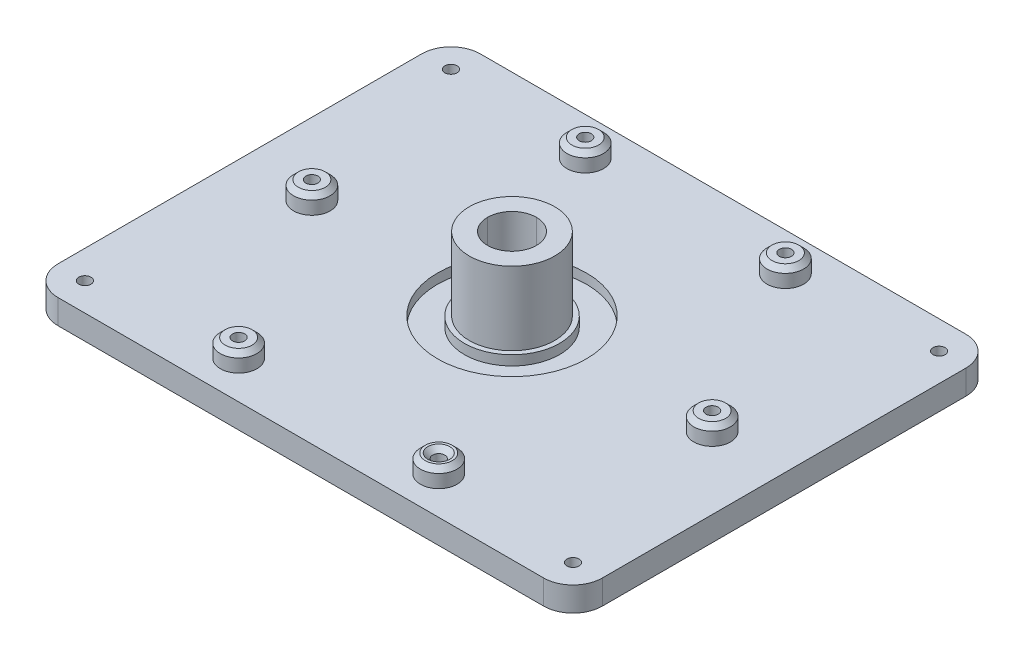
SolidWorks part; units mm, degrees
ref_plane "Front Plane" through (0, 0, 0) normal (0, 0, 1) x (1, 0, 0)
ref_plane "Top Plane" through (0, 0, 0) normal (0, 1, 0) x (1, 0, 0)
ref_plane "Right Plane" through (0, 0, 0) normal (1, 0, 0) x (0, 0, -1)
sketch "Sketch1" plane through (0, 0, 0) normal (0, 1, 0) x (1, 0, 0)
  line L1 (-100, 75) -> (100, 75) construction
  line L2 (-100, 75) -> (-100, -75) construction
  line L3 (-100, -75) -> (100, -75) construction
  line L4 (100, 75) -> (100, -75) construction
  line L5 (-100, 75) -> (100, -75) construction
  line L6 (-100, -75) -> (100, 75) construction
  line L7 (-99.5, 86.5) -> (99.5, 86.5)
  line L8 (-111.5, 74.5) -> (-111.5, -74.5)
  line L9 (-99.5, -86.5) -> (99.5, -86.5)
  line L10 (111.5, 74.5) -> (111.5, -74.5)
  line L11 (-111.5, 86.5) -> (111.5, -86.5) construction
  line L12 (-111.5, -86.5) -> (111.5, 86.5) construction
  circle A0 centre (100, 75) radius 2.5
  circle A1 centre (100, -75) radius 2.5
  circle A2 centre (-100, -75) radius 2.5
  circle A3 centre (-100, 75) radius 2.5
  arc A4 (99.5, -86.5) -> (111.5, -74.5) centre (99.5, -74.5) ccw
  arc A5 (-111.5, -74.5) -> (-99.5, -86.5) centre (-99.5, -74.5) ccw
  arc A6 (-99.5, 86.5) -> (-111.5, 74.5) centre (-99.5, 74.5) ccw
  arc A7 (99.5, 86.5) -> (111.5, 74.5) centre (99.5, 74.5) cw
  point P0 (0, 0)
  point P10 (0, 0)
  dimension "D3" = 5
  dimension "D4" = 5
  dimension "D5" = 5
  dimension "D6" = 5
  dimension "D9" = 12
  dimension "D1" = 150
  dimension "D2" = 200
  dimension "D7" = 173
  dimension "D8" = 223
extrude "Boss-Extrude1" add sketch "Sketch1" against normal blind 10
sketch "Sketch2" plane through (0, 0, 0) normal (0, 1, 0) x (1, 0, 0)
  circle A0 centre (0, 0) radius 30.5
  circle A1 centre (0, 0) radius 19.5
  dimension "D1" = 61
  dimension "D2" = 39
extrude "Cut-Extrude1" cut sketch "Sketch2" against normal blind 4
sketch "Sketch3" plane through (0, 0, 0) normal (0, 1, 0) x (1, 0, 0)
  circle A0 centre (0, 0) radius 17.5
  dimension "D1" = 35
extrude "Boss-Extrude2" add sketch "Sketch3" along normal blind 30
sketch "Sketch6" plane through (0, 0, 0) normal (1, 0, 0) x (0, 0, -1)
  line L0 (17.5, 30) -> (-17.5, 30) construction
  line L1 (-10, 30) -> (10, 30)
  line L2 (-10, 30) -> (-10, -2.5)
  line L3 (-10, -10) -> (10, -10)
  line L4 (10, 30) -> (10, -10)
  line L5 (-74.5, -10) -> (74.5, -10) construction
  line L6 (-10, -10) -> (-17.5, -10)
  line L7 (-17.5, -10) -> (-10, -2.5)
  point P8 (0, 30)
  dimension "D1" = 20
extrude "Cut-Extrude2" cut sketch "Sketch6" against normal mid plane 20
fillet "Fillet1" radius 10 4 edges at (10, 13.75, 10) (-10, 13.75, 10) (-10, 10, -10) (10, 10, -10)
sketch "Sketch9" plane through (0, 0, 0) normal (0, 1, 0) x (1, 0, 0)
  line L7 (82, 0) -> (41, 71.0141) construction
  line L8 (41, 71.0141) -> (-41, 71.0141) construction
  line L9 (-41, 71.0141) -> (-82, 0) construction
  line L10 (-82, 0) -> (-41, -71.0141) construction
  line L11 (-41, -71.0141) -> (41, -71.0141) construction
  line L12 (41, -71.0141) -> (82, 0) construction
  circle A0 centre (0, 0) radius 70 construction
  circle A9 centre (0, 0) radius 71.0141 construction
  circle A10 centre (41, 71.0141) radius 12 construction
  circle A11 centre (41, 71.0141) radius 2.5
  circle A12 centre (82, 0) radius 2.5
  circle A13 centre (41, -71.0141) radius 2.5
  circle A14 centre (-41, -71.0141) radius 2.5
  circle A15 centre (-82, 0) radius 2.5
  circle A16 centre (-41, 71.0141) radius 2.5
  dimension "D1" = 140
  dimension "D2" = 24
  dimension "D3" = 5
extrude "Cut-Extrude4" cut sketch "Sketch9" against normal blind 20
sketch "Sketch10" plane through (0, 0, 0) normal (0, 1, 0) x (1, 0, 0)
  circle A0 centre (41, 71.0141) radius 2.5
  circle A1 centre (41, 71.0141) radius 7.5
  circle A2 centre (82, 0) radius 7.5
  circle A3 centre (82, 0) radius 2.5
  circle A4 centre (41, -71.0141) radius 7.5
  circle A5 centre (41, -71.0141) radius 2.5
  circle A6 centre (-41, -71.0141) radius 7.5
  circle A7 centre (-41, -71.0141) radius 2.5
  circle A8 centre (-82, 0) radius 7.5
  circle A9 centre (-82, 0) radius 2.5
  circle A10 centre (-41, 71.0141) radius 7.5
  circle A11 centre (-41, 71.0141) radius 2.5
  dimension "D1" = 15
extrude "Boss-Extrude3" add sketch "Sketch10" along normal blind 7.38
chamfer "Chamfer1" distance 2 angle 45 7 edges at (41, 7.38, -63.5141) (41, 7.38, 73.5141) (41, 7.38, 78.5141) (-82, 7.38, 7.5) (-41, 7.38, 78.5141) (82, 7.38, 7.5) (-41, 7.38, -63.5141)
